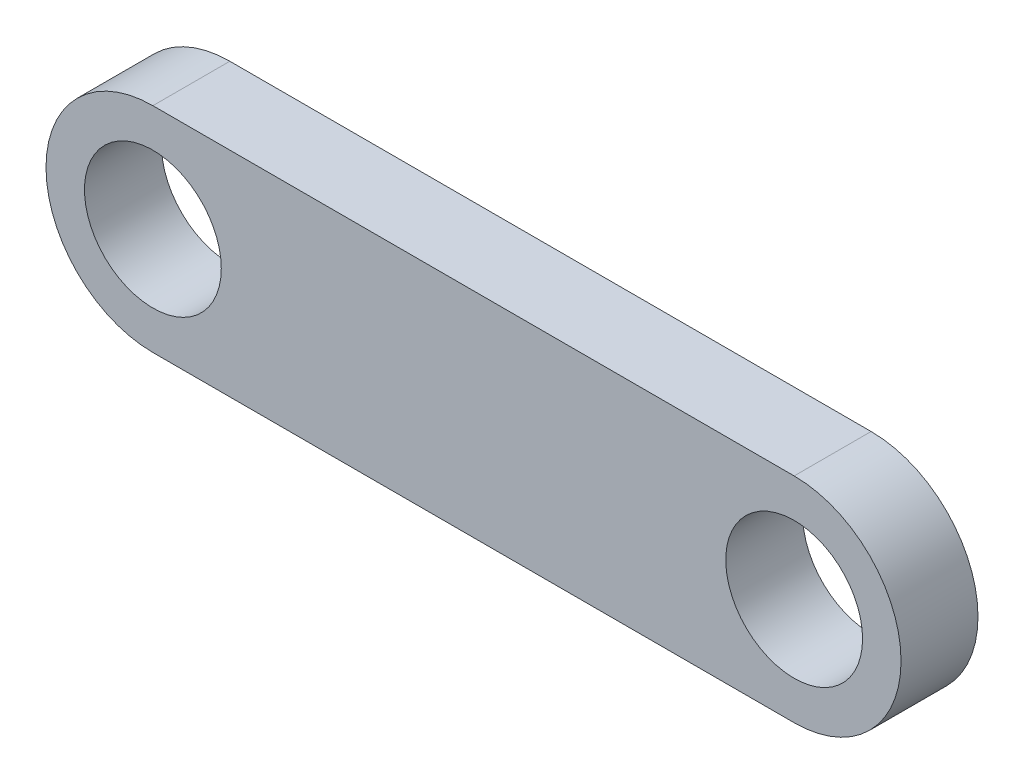
SolidWorks part; units mm, degrees
material "POM Acetal Copolymer"
ref_plane "Front Plane" through (0, 0, 0) normal (0, 0, 1) x (1, 0, 0)
ref_plane "Top Plane" through (0, 0, 0) normal (0, 1, 0) x (1, 0, 0)
ref_plane "Right Plane" through (0, 0, 0) normal (1, 0, 0) x (0, 0, -1)
sketch "Sketch1" plane through (0, 0, 0) normal (0, 0, 1) x (1, 0, 0)
  line L0 (-7.5, 3.7924) -> (-7.5, -3.5546) construction
  line L1 (-7.5, 3.5) -> (7.5, 3.5)
  line L7 (7.5, 3.7924) -> (7.5, -3.5201) construction
  line L8 (0, -6.7234) -> (0, 6.7234) construction
  line L9 (-10.6587, 1) -> (10.897, 1) construction
  line L12 (7.5, -1.5) -> (-7.5, -1.5)
  line L13 (-7.5, -1.5) -> (7.5, -1.5) construction
  circle A0 centre (-7.5, 1) radius 2.5
  circle A1 centre (7.5, 1) radius 2.5
  circle A2 centre (-7.5, 1) radius 1.6
  circle A3 centre (7.5, 1) radius 1.6
  point P0 (0, 0)
  point P22 (0, 0)
  dimension "D4" = 7.5
  dimension "D3" = 7.5
extrude "Boss-Extrude2" add sketch "Sketch1" along normal blind 0.9 and the other way blind 0.9 contours A1 L1 A0 L12 | A0 A2 | A1 A3 region at (0, 1, 0) region at (-5.7822, 2.7178, 0) region at (9.2178, 2.7178, 0)
